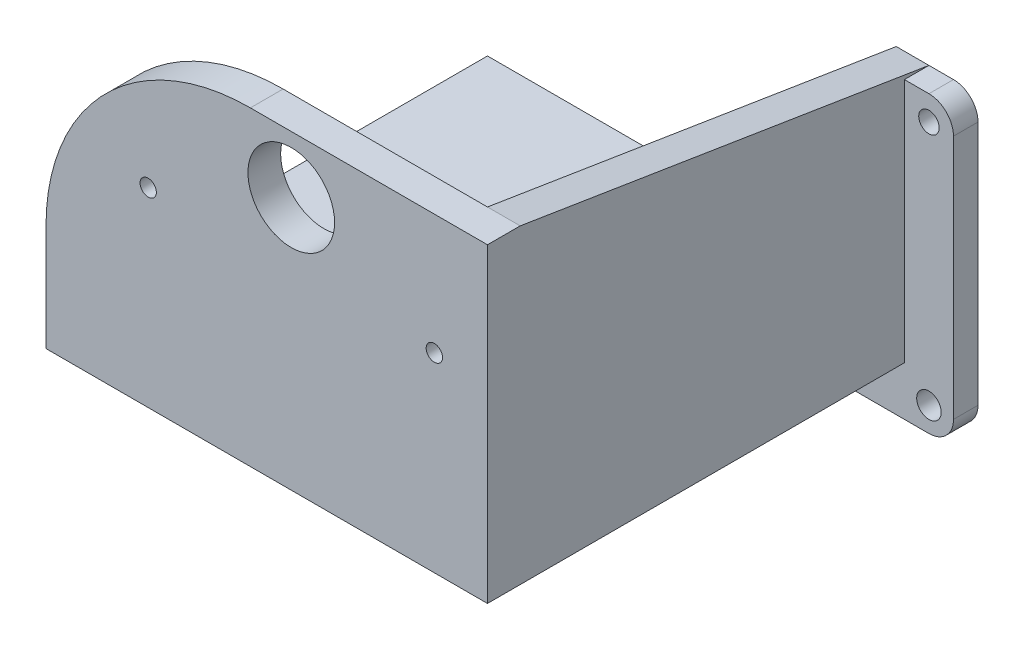
SolidWorks part; units mm, degrees
ref_plane "Plano frontal" through (0, 0, 0) normal (0, 0, 1) x (1, 0, 0)
ref_plane "Plano superior" through (0, 0, 0) normal (0, 1, 0) x (1, 0, 0)
ref_plane "Plano direito" through (0, 0, 0) normal (1, 0, 0) x (0, 0, -1)
sketch "Esboço1" plane through (0, 0, 0) normal (0, 0, 1) x (1, 0, 0)
  line L1 (-27, -19) -> (27, -19)
  line L2 (-27, -19) -> (-27, 19)
  line L3 (-27, 19) -> (27, 19)
  line L4 (27, -19) -> (27, 19)
  line L5 (-27, -19) -> (27, 19) construction
  line L6 (-27, 19) -> (27, -19) construction
  point P0 (0, 0)
  dimension "D1" = 54
  dimension "D2" = 38
extrude "Ressalto-extrusão1" add sketch "Esboço1" along normal blind 4
sketch "Esboço2" plane through (0, 0, 0) normal (0, 0, -1) x (-1, 0, 0)
  line L0 (-27, 19) -> (-23, 19)
  line L9 (-27, 19) -> (27, 19) construction
  line L10 (-23, 19) -> (-23, -15)
  line L11 (-23, -15) -> (27, -15)
  line L12 (27, 19) -> (27, -19) construction
  line L13 (27, -15) -> (27, -19)
  line L14 (27, -19) -> (-27, -19)
  line L15 (-27, -19) -> (-27, 19)
  dimension "D1" = 4
  dimension "D2" = 4
extrude "Ressalto-extrusão2" add sketch "Esboço2" along normal blind 50
sketch "Esboço6" plane through (27, 0, 0) normal (1, 0, 0) x (0, 0, -1)
  line L0 (0, 19) -> (50, 11)
  line L1 (-4, 19) -> (50, 19) construction
  line L2 (50, 19) -> (50, -19) construction
  line L3 (50, 11) -> (50, 19)
  line L4 (50, 19) -> (0, 19)
  line L5 (-4, -19) -> (-4, 19) construction
  dimension "D1" = 4
  dimension "D2" = 8
extrude "Corte-extrusão3" cut sketch "Esboço6" against normal up to next
sketch "Esboço3" plane through (0, 0, -50) normal (0, 0, -1) x (-1, 0, 0)
  line L0 (-27, 11) -> (-33, 11)
  line L1 (-33, 11) -> (-33, -25)
  line L2 (-33, -25) -> (27, -25)
  line L3 (-27, 11) -> (-27, -19)
  line L4 (-27, -19) -> (27, -19)
  line L5 (27, -19) -> (27, -25)
  line L6 (-23, 11) -> (-27, 11) construction
  point P4 (0, 0)
  dimension "D1" = 6
  dimension "D2" = 6
  dimension "D3" = 0
extrude "Ressalto-extrusão3" add sketch "Esboço3" against normal blind 3
fillet "Filete1" radius 3 3 edges at (33, -25, -48.5) (-27, -25, -48.5) (33, 11, -48.5)
sketch "Esboço4" plane through (0, 0, -47) normal (0, 0, 1) x (1, 0, 0)
  line L0 (33, 8) -> (33, -22) construction
  line L1 (27, 11) -> (30, 11) construction
  line L2 (30, -25) -> (-24, -25) construction
  line L3 (-27, -22) -> (-27, -19) construction
  circle A0 centre (-24, -22) radius 1.5
  circle A1 centre (30, -22) radius 1.5
  circle A3 centre (30, 8) radius 1.25
  dimension "D1" = 2.5
  dimension "D2" = 3
  dimension "D3" = 3
  dimension "D4" = 3
  dimension "D5" = 3
  dimension "D6" = 3
  dimension "D7" = 3
  dimension "D8" = 3
  dimension "D9" = 3
extrude "Corte-extrusão1" cut sketch "Esboço4" against normal through all
sketch "Esboço5" plane through (0, 0, 4) normal (0, 0, 1) x (1, 0, 0)
  line L0 (33, 8) -> (33, -22) construction
  line L1 (30, -25) -> (-24, -25) construction
  circle A0 centre (-14.5, 4.3) radius 1
  circle A1 centre (20.5, 4.3) radius 1
  circle A2 centre (3, 12) radius 5.3
  dimension "D1" = 17.5
  dimension "D2" = 17.5
  dimension "D3" = 2
  dimension "D4" = 2
  dimension "D5" = 7.7
  dimension "D6" = 0
  dimension "D7" = 10.6
  dimension "D8" = 30
  dimension "D9" = 37
extrude "Corte-extrusão2" cut sketch "Esboço5" against normal through all
fillet "Filete2" radius 25 1 edges at (-27, 19, 2)
sketch "Esboço7" plane through (0, -19, 0) normal (0, -1, 0) x (1, 0, 0)
  line L0 (27, 4) -> (27, -47) construction
  line L1 (-27, 4) -> (27, 4) construction
  circle A0 centre (3, -14.3) radius 1.25
  circle A1 centre (3, -22.3) radius 1.25
  dimension "D1" = 24
  dimension "D2" = 0
  dimension "D3" = 8
  dimension "D4" = 18.3
  dimension "D5" = 2.5
  dimension "D6" = 2.5
extrude "Corte-extrusão4" cut sketch "Esboço7" against normal through all
